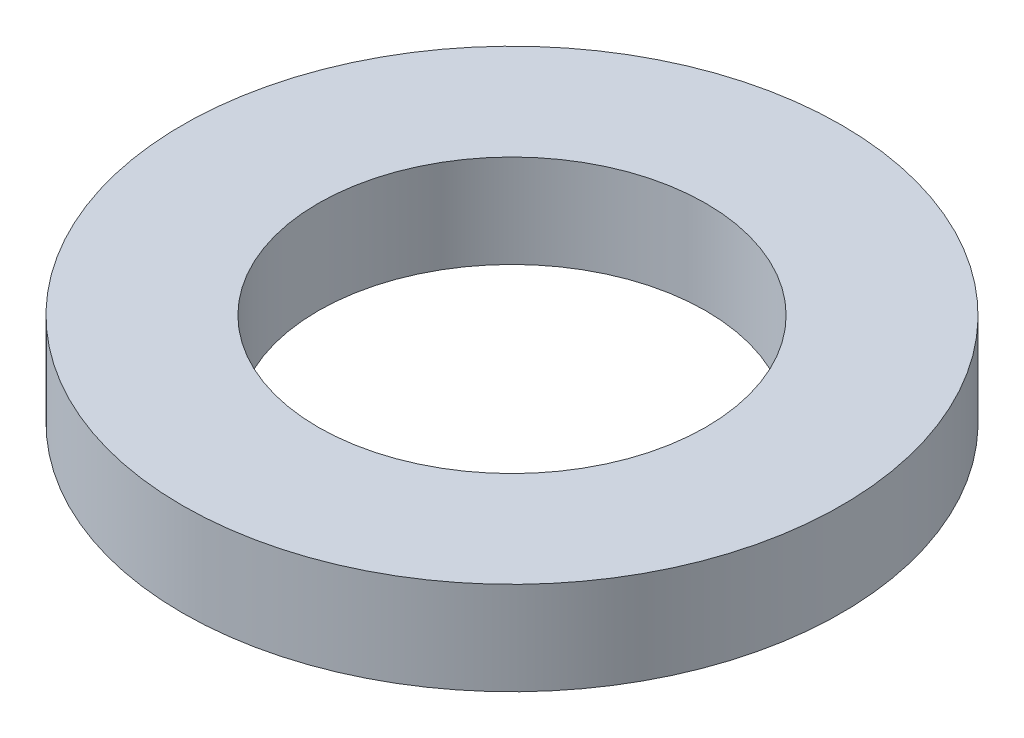
SolidWorks part; units mm, degrees
ref_plane "Front Plane" through (0, 0, 0) normal (0, 0, 1) x (1, 0, 0)
ref_plane "Top Plane" through (0, 0, 0) normal (0, 1, 0) x (1, 0, 0)
ref_plane "Right Plane" through (0, 0, 0) normal (1, 0, 0) x (0, 0, -1)
sketch "Sketch1" plane through (0, 0, 0) normal (0, 1, 0) x (1, 0, 0)
  circle A0 centre (0, 0) radius 85
  dimension "FLANGE_OD" = 170
extrude "Boss-Extrude1" add sketch "Sketch1" along normal blind 24
sketch "Sketch2" plane through (0, 0, 0) normal (0, 1, 0) x (1, 0, 0)
  circle A0 centre (0, 0) radius 50
  dimension "BORE_D" = 100
extrude "Cut-Extrude1" cut sketch "Sketch2" along normal through all
sketch "Sketch3" plane through (0, 24, 0) normal (0, 1, 0) x (1, 0, 0)
  circle A0 centre (0, 0) radius 34.7866 construction
  circle A1 centre (-34.7866, 0) radius 2.1929
  dimension "BOLT_D" = 4.3857
  dimension "BOLT_PCD" = 69.5732
extrude "Cut-Extrude2" cut sketch "Sketch3" against normal blind 16.2327 rebuild error yes
pattern_circular "CirPattern1" count 3 over 360 rebuild error yes
